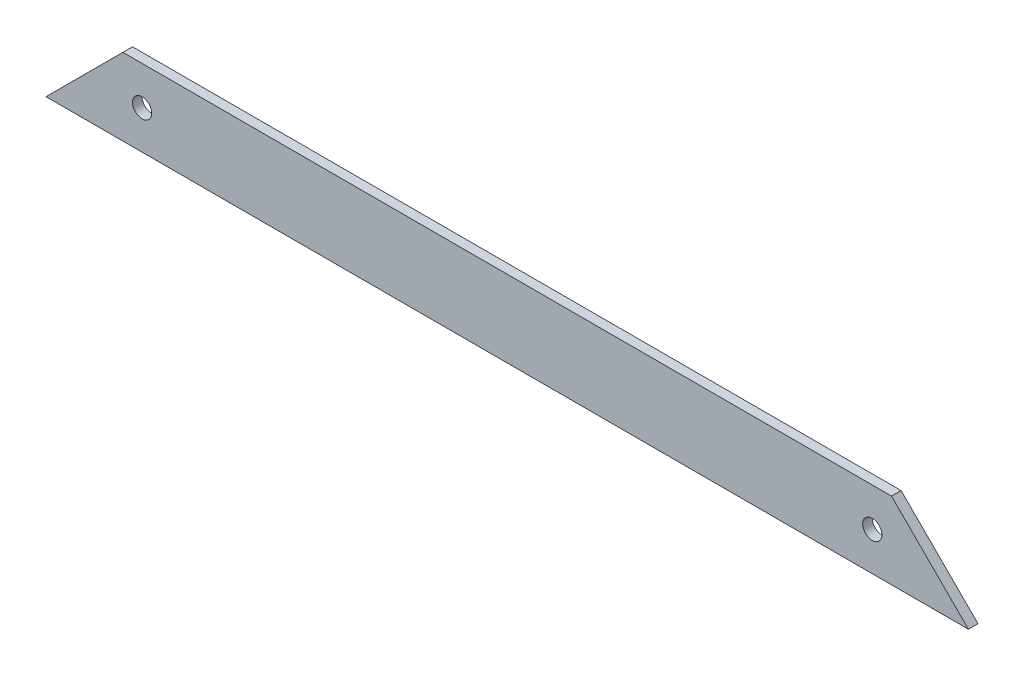
SolidWorks part; units mm, degrees
material "6061 Alloy"
ref_plane "Front Plane" through (0, 0, 0) normal (0, 0, 1) x (1, 0, 0)
ref_plane "Top Plane" through (0, 0, 0) normal (0, 1, 0) x (1, 0, 0)
ref_plane "Right Plane" through (0, 0, 0) normal (1, 0, 0) x (0, 0, -1)
ref_axis "Axis1" through (0, -67.7, 0) along (0, 1, 0)
sketch "Sketch3" plane through (0, 0, 0) normal (0, 0, 1) x (1, 0, 0)
  line L0 (127, 0) -> (-127, 0)
  line L1 (-127, 0) -> (-152.4, -25.4)
  line L2 (-152.4, -25.4) -> (152.4, -25.4)
  line L3 (0, -67.7) -> (0, 42.3) construction
  line L4 (0, 0) -> (0, -25.4) construction
  line L5 (127, 0) -> (152.4, -25.4)
  circle A0 centre (-120.65, -12.7) radius 3.175
  circle A1 centre (120.65, -12.7) radius 3.175
  dimension "D4" = 31.75
  dimension "D5" = 6.35
  dimension "D1" = 127
  dimension "D2" = 25.4
  dimension "D3" = 12.7
  dimension "D6" = 45
extrude "Boss-Extrude1" add sketch "Sketch3" along normal blind 3.175
